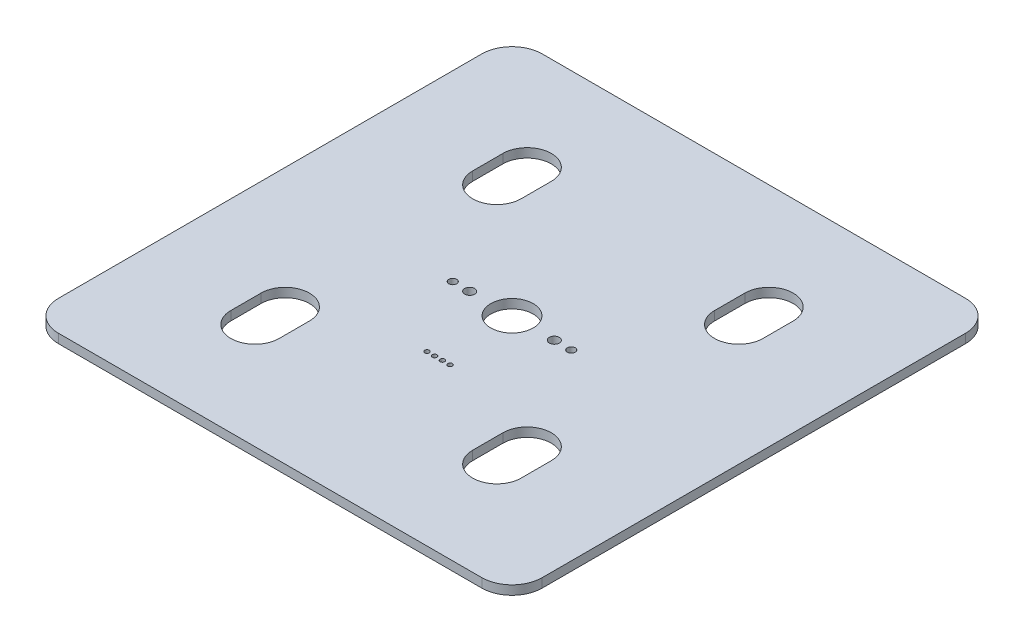
SolidWorks part; units mm, degrees
ref_plane "Front Plane" through (0, 0, 0) normal (0, 0, 1) x (1, 0, 0)
ref_plane "Top Plane" through (0, 0, 0) normal (0, 1, 0) x (1, 0, 0)
ref_plane "Right Plane" through (0, 0, 0) normal (1, 0, 0) x (0, 0, -1)
sketch "Sketch1" plane through (0, 0, 0) normal (0, 1, 0) x (1, 0, 0)
  line L1 (-40, -40) -> (40, -40)
  line L2 (-40, -40) -> (-40, 40)
  line L3 (-40, 40) -> (40, 40)
  line L4 (40, -40) -> (40, 40)
  line L5 (-40, -40) -> (40, 40) construction
  line L6 (-40, 40) -> (40, -40) construction
  point P0 (0, 0)
  dimension "D1" = 40
extrude "Boss-Extrude1" add sketch "Sketch1" along normal mid plane 1.5
fillet "Fillet1" radius 5 1 edges at (-40, 0, 40) type face fillet first side face at (0, 0, 40) second side face at (-40, 0, 0)
fillet "Fillet3" radius 5 1 edges at (-40, 0, -40) type face fillet first side face at (-40, 0, -2.5) second side face at (0, 0, -40)
fillet "Fillet4" radius 5 1 edges at (40, 0, -40) type face fillet first side face at (2.5, 0, -40) second side face at (40, 0, 0)
fillet "Fillet5" radius 5 1 edges at (40, 0, 40) type face fillet first side face at (40, 0, 2.5) second side face at (2.5, 0, 40)
sketch "Sketch2" plane through (0, 0.75, 0) normal (0, 1, 0) x (1, 0, 0)
  line L0 (0, 43.5966) -> (0, -43.8986) construction
  line L1 (-44.3014, 0) -> (44.9055, 0) construction
  line L2 (-20, 17.5) -> (-20, 22.5) construction
  line L3 (-24, 17.5) -> (-24, 22.5)
  line L4 (-16, 17.5) -> (-16, 22.5)
  line L5 (-20, -17.5) -> (-20, -22.5) construction
  line L6 (-16, -17.5) -> (-16, -22.5)
  line L7 (-24, -17.5) -> (-24, -22.5)
  line L8 (20, -17.5) -> (20, -22.5) construction
  line L9 (16, -17.5) -> (16, -22.5)
  line L10 (24, -17.5) -> (24, -22.5)
  line L11 (20, 17.5) -> (20, 22.5) construction
  line L12 (24, 17.5) -> (24, 22.5)
  line L13 (16, 17.5) -> (16, 22.5)
  arc A0 (-24, 17.5) -> (-16, 17.5) centre (-20, 17.5) ccw
  arc A1 (-16, 22.5) -> (-24, 22.5) centre (-20, 22.5) ccw
  arc A2 (-16, -17.5) -> (-24, -17.5) centre (-20, -17.5) ccw
  arc A3 (-24, -22.5) -> (-16, -22.5) centre (-20, -22.5) ccw
  arc A4 (16, -17.5) -> (24, -17.5) centre (20, -17.5) cw
  arc A5 (24, -22.5) -> (16, -22.5) centre (20, -22.5) cw
  arc A6 (24, 17.5) -> (16, 17.5) centre (20, 17.5) cw
  arc A7 (16, 22.5) -> (24, 22.5) centre (20, 22.5) cw
  point P7 (-20, 20)
  point P13 (-20, -20)
  point P22 (20, -20)
  point P29 (20, 20)
  dimension "D4" = 4
  dimension "D1" = 20
  dimension "D2" = 20
  dimension "D3" = 20
  dimension "D5" = 5
extrude "Cut-Extrude1" cut sketch "Sketch2" against normal through all both and the other way through all
sketch "Sketch3" plane through (0, 0.75, 0) normal (0, 1, 0) x (1, 0, 0)
  circle A0 centre (0, 0) radius 3.5
  dimension "D1" = 7
extrude "Cut-Extrude2" cut sketch "Sketch3" against normal through all both and the other way through all
sketch "Sketch4" plane through (0, 0.75, 0) normal (0, 1, 0) x (1, 0, 0)
  line L0 (-13.5506, -12.15) -> (0, -12.15) construction
  line L1 (0, 0) -> (0, -12.15) construction
  line L2 (0, 0) -> (-13.5506, 0) construction
  circle A2 centre (-0.635, -12.15) radius 0.38
  circle A3 centre (-1.905, -12.15) radius 0.38
  circle A5 centre (-9.8, 0) radius 0.65
  circle A6 centre (-7, 0) radius 0.825
  circle A7 centre (7, 0) radius 0.825
  circle A8 centre (9.8, 0) radius 0.65
  circle A9 centre (0.635, -12.15) radius 0.38
  circle A10 centre (1.905, -12.15) radius 0.38
  dimension "D4" = 0.76
  dimension "D7" = 1.3
  dimension "D8" = 1.65
  dimension "D1" = 0.635
  dimension "D2" = 7
  dimension "D3" = 9.8
  dimension "D5" = 1.27
  dimension "D6" = 12.15
extrude "Cut-Extrude3" cut sketch "Sketch4" against normal through all both and the other way through all
